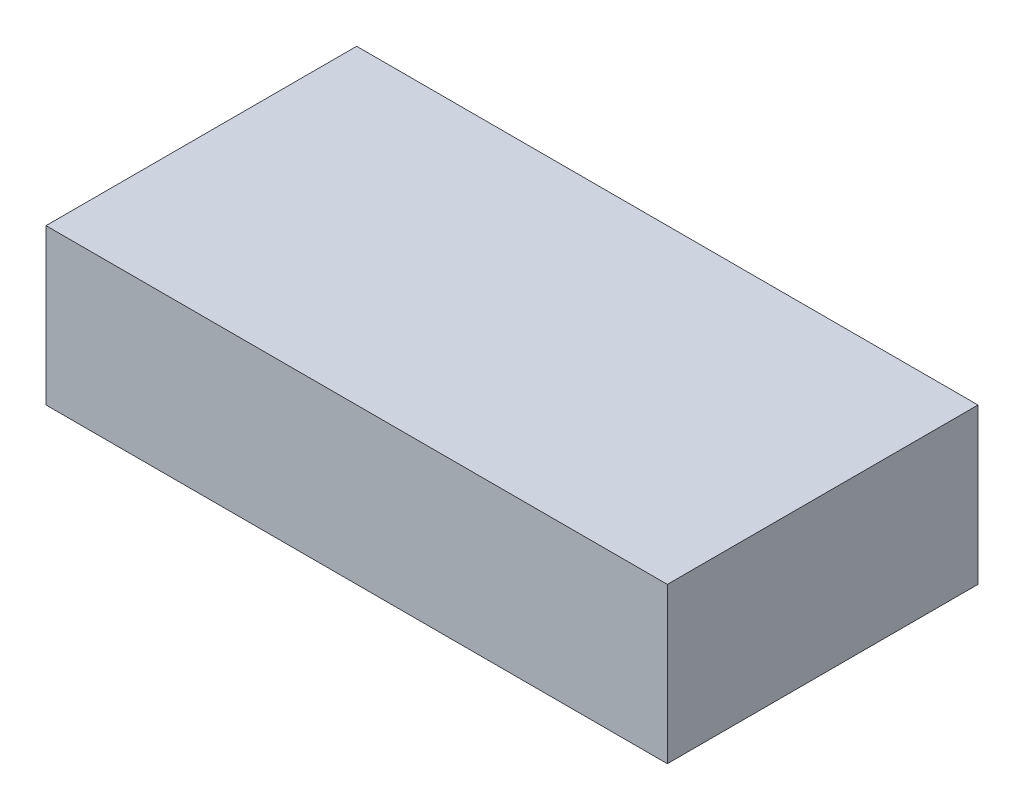
SolidWorks part; units mm, degrees
ref_plane "Front Plane" through (0, 0, 0) normal (0, 0, 1) x (1, 0, 0)
ref_plane "Top Plane" through (0, 0, 0) normal (0, 1, 0) x (1, 0, 0)
ref_plane "Right Plane" through (0, 0, 0) normal (1, 0, 0) x (0, 0, -1)
sketch "Sketch1" plane through (0, 0, 0) normal (0, 1, 0) x (1, 0, 0)
  line L1 (0, 0) -> (101.6, 0)
  line L2 (0, 0) -> (0, 50.8)
  line L3 (0, 50.8) -> (101.6, 50.8)
  line L4 (101.6, 0) -> (101.6, 50.8)
  dimension "D1" = 50.8
  dimension "D2" = 101.6
extrude "Boss-Extrude1" add sketch "Sketch1" along normal blind 25.4
sketch "Sketch3" plane through (0, 0, -50.8) normal (0, 0, -1) x (-1, 0, 0)
  line L0 (-9.6371, 1.6839) -> (-26.3979, 1.2539) construction
  line L1 (-22.2733, 1.3597) -> (-22.3052, 2.6039) construction
  line L2 (-30.5582, 1.4284) -> (-33.3342, 1.3572) construction
  line L3 (-33.8083, 19.8389) -> (-31.0323, 19.9101) construction
  line L6 (-9.4547, 20.7448) -> (-26.8864, 20.2977) construction
  line L12 (-9.6371, 1.6839) -> (-26.3979, 1.2539)
  line L13 (-22.2733, 1.3597) -> (-22.3052, 2.6039)
  line L14 (-30.5582, 1.4284) -> (-33.3342, 1.3572)
  line L15 (-33.8083, 19.8389) -> (-31.0323, 19.9101)
  line L16 (-9.4547, 20.7448) -> (-26.8864, 20.2977)
  arc A0 (-37.079, 3.3429) -> (-33.3342, 1.3572) centre (-30.7952, 10.6693) ccw construction
  arc A1 (-37.4464, 17.6638) -> (-37.079, 3.3429) centre (-30.7952, 10.6693) ccw construction
  arc A2 (-33.8083, 19.8389) -> (-37.4464, 17.6638) centre (-30.7952, 10.6693) ccw construction
  arc A3 (-37.079, 3.3429) -> (-33.3342, 1.3572) centre (-30.7952, 10.6693) ccw
  arc A4 (-37.4464, 17.6638) -> (-37.079, 3.3429) centre (-30.7952, 10.6693) ccw
  arc A5 (-33.8083, 19.8389) -> (-37.4464, 17.6638) centre (-30.7952, 10.6693) ccw
  ellipse E0 centre (-9.229, -1730.8447) end of major axis (-22.7937, -4053.9835) minor radius 12.7 (-7.3727, 18.4353) -> (-7.5452, 4.1005) ccw construction
  ellipse E1 centre (-9.229, -1730.8447) end of major axis (-22.7937, -4053.9835) minor radius 12.7 (-7.3727, 18.4353) -> (-7.5452, 4.1005) ccw
  spline S0 degree 3 poles (55.1805, 6000.222) (-29.6812, -19.96) (0.1704, -0.8064) (-28.7521, 1.3807) (-29.1104, 1.4051) (-71.6476, 3.094) (-156.209, -134.3228) (-591.201, -5969.7308) knots -19.845745 -19.845745 -19.845745 -19.845745 0.5 0.5 0.75 0.75 30.073398 30.073398 30.073398 30.073398 only from (-26.3979, 1.2539) to (-30.5582, 1.4284) construction
  spline S1 degree 3 poles (-1052.385, 5929.5752) (-169.9706, 144.1601) (-71.3435, 16.2013) (-29.5902, 20.0074) (-29.2373, 20.0497) (-28.5386, 20.1386) (-28.1949, 20.185) (-2.2216, 23.1153) (-27.6879, -23.1161) (238.0637, -5973.299) knots -28.722115 -28.722115 -28.722115 -28.722115 0.25 0.25 0.5 0.5 0.75 0.75 19.975805 19.975805 19.975805 19.975805 only from (-31.0323, 19.9101) to (-26.8864, 20.2977) construction
  spline S2 degree 3 poles (-5855.7376, -1317.5672) (-292.0673, -95.3627) (-2.38, -1.3108) (-7.4772, 19.1344) (-7.5397, 19.2947) (-7.6899, 19.5894) (-7.7779, 19.7242) (-7.9651, 19.9652) (-8.0658, 20.0735) (-8.3799, 20.3636) (-8.597, 20.5056) (-27.6797, 29.0096) (-13.7285, -321.2543) (3321.0321, -4964.3394) knots -14.722216 -14.722216 -14.722216 -14.722216 0.125 0.125 0.25 0.25 0.375 0.375 0.5 0.5 0.75 0.75 22.281593 22.281593 22.281593 22.281593 only from (-7.3727, 18.4353) to (-9.4547, 20.7448) construction
  spline S3 degree 3 poles (830.3205, 5941.9912) (-1.686, 347.6847) (-27.8452, -7.6744) (-8.8945, 1.9158) (-8.7848, 1.9833) (-8.5703, 2.1396) (-8.4645, 2.2287) (-8.258, 2.4313) (-8.1567, 2.5455) (-7.9696, 2.7951) (-7.8827, 2.9309) (-7.7295, 3.232) (-7.6657, 3.3922) (-3.5795, 18.6981) (-148.7389, 107.1015) (-4017.3906, -4453.8907) knots -21.391082 -21.391082 -21.391082 -21.391082 0.25 0.25 0.375 0.375 0.5 0.5 0.625 0.625 0.75 0.75 0.875 0.875 11.890353 11.890353 11.890353 11.890353 only from (-9.6371, 1.6839) to (-7.5452, 4.1005) construction
  spline S4 degree 3 poles (-26.3979, 1.2539) (-27.0321, 1.2377) (-27.6989, 1.301) (-28.7521, 1.3807) (-29.1104, 1.4051) (-29.8296, 1.4336) (-30.1922, 1.4378) (-30.5582, 1.4284) knots 0 0 0 0 0.5 0.5 0.75 0.75 1 1 1 1
  spline S5 degree 3 poles (-31.0323, 19.9101) (-30.6661, 19.9195) (-30.3046, 19.9423) (-29.5902, 20.0074) (-29.2373, 20.0497) (-28.5386, 20.1386) (-28.1949, 20.185) (-27.5281, 20.2602) (-27.2033, 20.2895) (-26.8864, 20.2977) knots 0 0 0 0 0.25 0.25 0.5 0.5 0.75 0.75 1 1 1 1
  spline S6 degree 3 poles (-7.3727, 18.4353) (-7.3705, 18.6171) (-7.3921, 18.793) (-7.4772, 19.1344) (-7.5397, 19.2947) (-7.6899, 19.5894) (-7.7779, 19.7242) (-7.9651, 19.9652) (-8.0658, 20.0735) (-8.3799, 20.3636) (-8.597, 20.5056) (-9.035, 20.7009) (-9.2496, 20.7501) (-9.4547, 20.7448) knots 0 0 0 0 0.125 0.125 0.25 0.25 0.375 0.375 0.5 0.5 0.75 0.75 1 1 1 1
  spline S7 degree 3 poles (-9.6371, 1.6839) (-9.4326, 1.6891) (-9.221, 1.7506) (-8.8945, 1.9158) (-8.7848, 1.9833) (-8.5703, 2.1396) (-8.4645, 2.2287) (-8.258, 2.4313) (-8.1567, 2.5455) (-7.9696, 2.7951) (-7.8827, 2.9309) (-7.7295, 3.232) (-7.6657, 3.3922) (-7.574, 3.7357) (-7.5474, 3.9168) (-7.5452, 4.1005) knots 0 0 0 0 0.25 0.25 0.375 0.375 0.5 0.5 0.625 0.625 0.75 0.75 0.875 0.875 1 1 1 1
extrude "Cut-Extrude1" cut sketch "Sketch3" against normal blind 19.05 from offset 8.382 contours L12 S7 E1 S6 L16 S5 L15 A5 A4 A3 L14 S4 region at (23.0559, 10.9044, -50.8) offset against normal yes
sketch "Sketch5" plane through (0, 25.4, 0) normal (0, 1, 0) x (1, 0, 0)
  line L0 (0, 23.368) -> (40.4472, 23.368)
  line L1 (0, 50.8) -> (0, 0) construction
  line L2 (0, 0) -> (101.6, 0) construction
  line L3 (0, 42.418) -> (40.4472, 42.418)
  line L4 (101.6, 50.8) -> (0, 50.8) construction
  line L5 (40.4472, 23.368) -> (40.4472, 42.418)
  line L6 (28.2562, 0) -> (40.4472, 0) construction
  line L7 (28.2562, 0) -> (40.4472, 0)
  line L8 (0, 23.368) -> (0, 42.418)
  line M2 (0, 50.8) -> (0, 0)
  dimension "D1" = 23.368
  dimension "D2" = 8.382
extrude "Cut-Extrude2" cut sketch "Sketch5" against normal up to surface and the other way up to surface from offset 12.7 contours L0 L5 L3 M2 region at (20.2236, 25.4, -32.893) up to face at (13.8273, 1.5764, -28.1305) other way up to face at (13.8126, 20.6331, -28.1305) offset against normal yes
